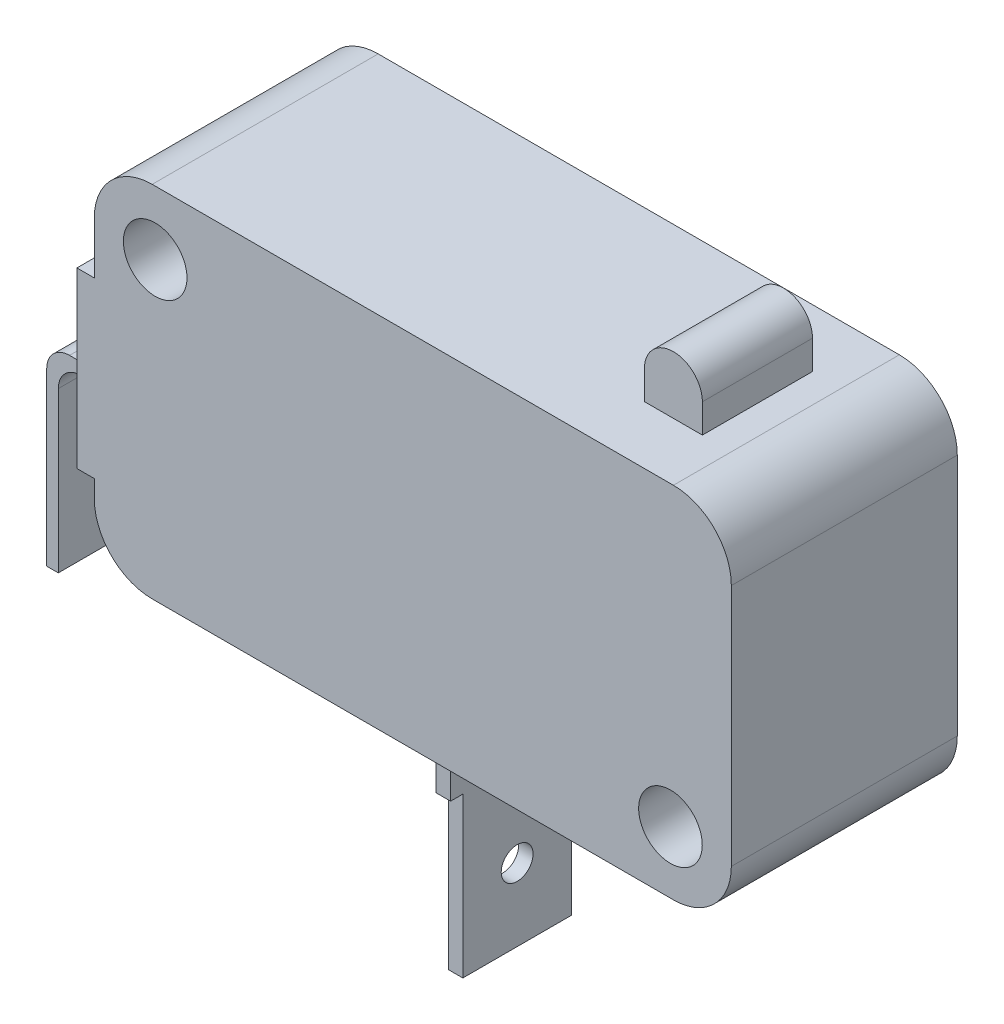
SolidWorks part; units mm, degrees
note: '?' marks a value the reader was unsure of. The reader was unsure of these and kept them because the rebuilt part matched: shared geometry of "Sketch".
ref_plane "Front Plane" through (0, 0, 0) normal (0, 0, 1) x (1, 0, 0)
ref_plane "Top Plane" through (0, 0, 0) normal (0, 1, 0) x (1, 0, 0)
ref_plane "Right Plane" through (0, 0, 0) normal (1, 0, 0) x (0, 0, -1)
sketch "Sketch1" plane through (0, 0, 0) normal (0, 0, 1) x (1, 0, 0)
  line L0 (0, 7.874) -> (0, -7.874) construction
  line L1 (-13.97, 0) -> (13.97, 0) construction
  line L2 (11.43, 7.874) -> (-11.43, 7.874)
  line L3 (-13.97, 5.334) -> (-13.97, 3.048)
  line L4 (-13.97, 3.048) -> (-14.732, 3.048)
  line L5 (-14.732, 3.048) -> (-14.732, -4.572)
  line L6 (-14.732, -4.572) -> (-13.97, -4.572)
  line L7 (-13.97, -4.572) -> (-13.97, -5.334)
  line L8 (-11.43, -7.874) -> (11.43, -7.874)
  line L9 (13.97, -5.334) -> (13.97, 5.334)
  arc A0 (-11.43, 7.874) -> (-13.97, 5.334) centre (-11.43, 5.334) ccw
  arc A1 (-13.97, -5.334) -> (-11.43, -7.874) centre (-11.43, -5.334) ccw
  arc A2 (11.43, -7.874) -> (13.97, -5.334) centre (11.43, -5.334) ccw
  arc A3 (13.97, 5.334) -> (11.43, 7.874) centre (11.43, 5.334) ccw
  circle A4 centre (-11.3, 5.08) radius 1.395
  circle A5 centre (11.3, -5.16) radius 1.395
  dimension "D3" = 2.54
  dimension "D8" = 2.79
  dimension "D1" = 28.702
  dimension "D2" = 15.748
  dimension "D4" = 7.874
  dimension "D5" = 7.62
  dimension "D6" = 4.826
  dimension "D7" = 0.762
  dimension "D9" = 11.3
  dimension "D10" = 5.08
  dimension "D11" = 11.3
  dimension "D12" = 5.16
extrude "Extrude1" add sketch "Sketch1" along normal mid plane 9.91 contours A4 | L9 A3 L2 A0 L3 L4 L5 L6 L7 A1 L8 A2 A5 A4 | A5
sketch "Sketch2" plane through (0, 0, 0) normal (0, 0, 1) x (1, 0, 0)
  line L0 (-24.638, -2.794) -> (-14.732, -2.794)
  line L1 (-14.732, -2.286) -> (-24.638, -2.286)
  line L2 (-24.638, -2.286) -> (-24.638, -2.794)
  line L3 (-24.638, 1.27) -> (-14.732, 1.27)
  line L4 (-14.732, 1.778) -> (-24.638, 1.778)
  line L5 (-24.638, 1.778) -> (-24.638, 1.27)
  line L6 (0, 0) -> (-27.6869, 0) construction
  line L7 (-17.907, -2.794) -> (-17.907, -10.795)
  line L8 (-14.732, 1.778) -> (-14.732, 1.27)
  line L9 (-14.732, -2.286) -> (-14.732, -2.794)
  line L10 (-14.732, 3.048) -> (-14.732, -4.572) construction
  line L11 (-17.907, -10.795) -> (-17.399, -10.795)
  line L12 (-17.399, -10.795) -> (-17.399, -2.794)
  line L13 (-17.907, -2.794) -> (-17.907, -2.286)
  dimension "D1" = 3.556
  dimension "D2" = 1.27
  dimension "D3" = 0.508
  dimension "D4" = 0.508
  dimension "D5" = 9.906
  dimension "D6" = 9.906
  dimension "D7" = 3.175
  dimension "D8" = 8.509
extrude "Extrude2" add sketch "Sketch2" along normal mid plane 6.21 contours L9 L1 L2 L0 | L11 L12 L0 L7
sketch "Sketch3" plane through (0, 0, 0) normal (0, 0, 1) x (1, 0, 0)
  line L0 (0, 0) -> (0, 7.874) construction
  line L2 (10.16, 7.874) -> (10.16, 9.139)
  line L3 (7.62, 9.139) -> (7.62, 7.874)
  line L4 (7.62, 7.874) -> (10.16, 7.874)
  line L5 (-3.048, 7.874) -> (-2.54, 7.874)
  line L6 (-2.54, 7.874) -> (-2.54, 9.398)
  line L7 (-2.54, 9.398) -> (47.1735, 13.839)
  line L8 (47.1735, 13.839) -> (47.1283, 14.345)
  line L9 (47.1283, 14.345) -> (-3.048, 9.8626)
  line L10 (-3.048, 9.8626) -> (-3.048, 7.874)
  line L11 (11.43, 7.874) -> (-11.43, 7.874) construction
  arc A0 (10.16, 9.139) -> (7.62, 9.139) centre (8.89, 9.139) ccw
  dimension "D5" = 1.265
  dimension "D6" = 47.1735
  dimension "D7" = 47.1283
  dimension "D1" = 2.54
  dimension "D2" = 10.16
  dimension "D3" = 0.508
  dimension "D4" = 2.54
  dimension "D8" = 1.524
  dimension "D9" = 95.105
extrude "Extrude3" add sketch "Sketch3" along normal mid plane 4.83 contours L2 A0 L3 L4
sketch "Sketch4" plane through (0, 0, 0) normal (0, 0, 1) x (1, 0, 0)
  line L0 (-11.43, -7.874) -> (11.43, -7.874) construction
  line L1 (-0.38, -10.984) -> (-0.38, -18.034)
  line L2 (-0.38, -18.034) -> (-1.015, -18.034)
  line L3 (-1.015, -18.034) -> (-1.015, -10.414)
  line L6 (-0.38, -10.984) -> (-0.38, -7.874)
  line L7 (-0.38, -7.874) -> (-1.015, -7.874)
  line L8 (-1.015, -7.874) -> (-1.015, -10.414)
  line L9 (-1.015, -10.414) -> (-10.6125, -11.4524)
  line L11 (-10.5441, -12.0837) -> (-0.38, -10.984)
  line L18 (-10.6125, -11.4524) -> (-10.5441, -12.0837)
  dimension "D4" = 2.54
  dimension "D1" = 0.635
  dimension "D2" = 0.635
  dimension "D3" = 9.5975
  dimension "D5" = 3.11
  dimension "D6" = 0.38
  dimension "D7" = 10.16
extrude "Extrude4" add sketch "Sketch4" along normal mid plane 5.84 contours L11 L3 L2 L1 | L3 L11 L6 L7 L8
sketch "Sketch5" plane through (-1.015, -13.2508, 0) normal (-1, 0, 0) x (0, -1, 0)
  line L0 (-2.2018, -2.92) -> (-2.2018, -2.3813)
  line L1 (-2.2018, -2.3813) -> (4.7832, -2.3812)
  line L2 (-2.2018, 2.92) -> (-2.2018, 2.3812)
  line L3 (-2.2018, 2.3812) -> (4.7832, 2.3812)
  line L4 (-5.3768, -2.92) -> (4.7832, -2.92)
  line L5 (4.7832, -2.92) -> (4.7832, 2.92)
  line L6 (4.7832, 2.92) -> (-5.3768, 2.92)
  line L7 (-5.3768, 2.92) -> (-5.3768, -2.92)
  line L8 (-5.3768, -2.92) -> (4.7832, -2.92)
  line L9 (4.7832, -2.92) -> (4.7832, 2.92)
  line L12 (4.7832, 2.92) -> (-5.3768, 2.92)
  line L13 (-5.3768, 2.92) -> (-5.3768, -2.92)
  line L15 (4.7832, 0) -> (1.6082, 0) construction
  line L16 (4.7832, 2.92) -> (4.7832, -2.92) construction
  circle A0 centre (1.6082, 0) radius 0.6985
  dimension "D1" = 0
  dimension "D3" = 3.175
  dimension "D4" = 1.397
  dimension "D2" = 3.175
  dimension "D5" = 4.7625
extrude "Extrude5" cut sketch "Sketch5" against normal up to next
sketch "Sketch6" plane through (-17.399, 14.605, 0) normal (1, 0, 0) x (0, 1, 0)
  line L0 (-14.605, 0) -> (-17.399, 0) construction
  line L1 (-17.399, 3.105) -> (-17.399, -3.105) construction
  line L2 (-25.4, 3.105) -> (-25.4, -3.105) construction
  circle A0 centre (-22.352, 0) radius 0.635
  dimension "D1" = 1.27
  dimension "D2" = 3.048
extrude "Extrude7" cut sketch "Sketch6" against normal through all
extrude "Extrude8" cut sketch "Sketch" against normal mid plane 15.84 contours A4 | A5
sketch "Sketch" plane through (0, 0, 0) normal (0, 0, 1) x (1, 0, 0) same geometry as "Sketch1"
fillet "Fillet1" radius 1 2 edges at (-17.907, -2.286, 0) (-17.399, -2.794, 0)
sketch "Sketch7" plane through (-0.38, 0, 0) normal (1, 0, 0) x (0, 0, -1)
  point P0 (0, -14.859)
ref_plane "Plane1" through (0, -14.859, 0) normal (0, -1, 0) x (-1, 0, 0)
sketch "Sketch9" plane through (-17.399, 0, 0) normal (1, 0, 0) x (0, 0, -1)
  point P0 (0, -7.747)
ref_plane "Plane2" through (0, -7.747, 0) normal (0, -1, 0) x (-1, 0, 0)
sketch "0_0_Point" plane through (0, -14.859, 0) normal (0, -1, 0) x (-1, 0, 0)
  point P0 (0.6975, 0)
other "0_0" parameters "Diameter"=2, "StubLength"=2
ref_axis "Axis1" through (-0.6975, -24.859, 0) along (0, 1, 0)?
sketch "0_1_Point" plane through (0, -7.747, 0) normal (0, -1, 0) x (-1, 0, 0)
  point P0 (17.653, 0)
other "0_1" parameters "Diameter"=2, "StubLength"=2
ref_axis "Axis2" through (-17.653, -17.747, 0) along (0, 1, 0)?
